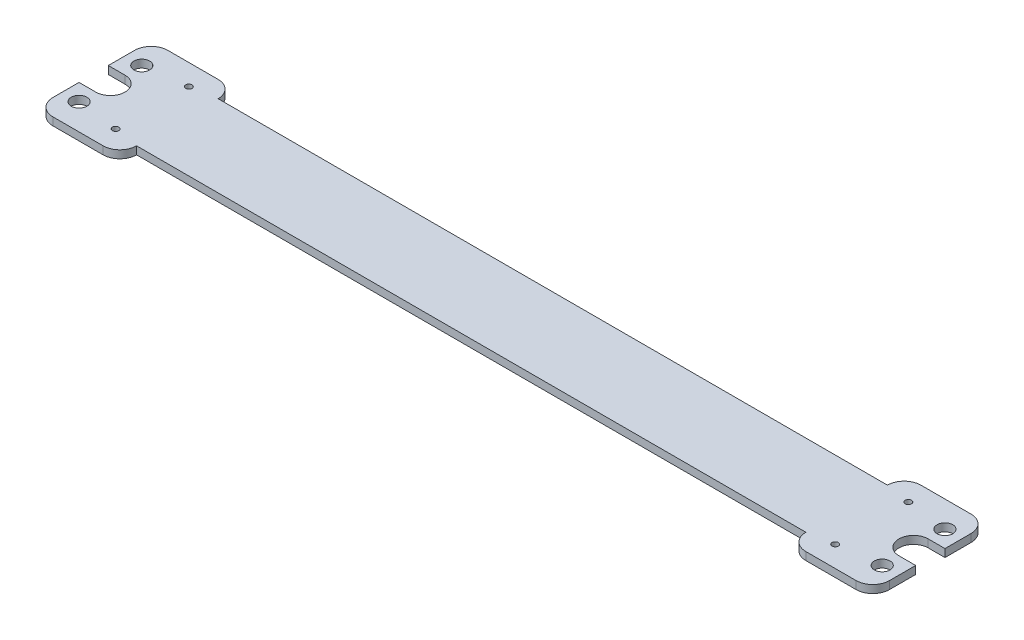
SolidWorks part; units mm, degrees
ref_plane "Front Plane" through (0, 0, 0) normal (0, 0, 1) x (1, 0, 0)
ref_plane "Top Plane" through (0, 0, 0) normal (0, 1, 0) x (1, 0, 0)
ref_plane "Right Plane" through (0, 0, 0) normal (1, 0, 0) x (0, 0, -1)
sketch "Sketch1" plane through (0, 0, 0) normal (0, 1, 0) x (1, 0, 0)
  line L0 (0, -34.925) -> (1.27, -34.925) construction
  line L1 (10.16, 0) -> (40.64, 0)
  line L2 (0, -10.16) -> (0, -26.035)
  line L3 (10.16, -69.85) -> (40.64, -69.85)
  line L5 (10.16, -43.815) -> (0, -43.815)
  line L6 (10.16, -26.035) -> (0, -26.035)
  line L7 (0, -43.815) -> (0, -59.69)
  line L8 (19.05, -34.925) -> (87.4324, -34.925) construction
  line L15 (50.8, -10.16) -> (254, -10.16)
  line L17 (50.8, -59.69) -> (254, -59.69)
  line L18 (254, -10.16) -> (254, -59.69)
  circle A0 centre (10.16, -53.975) radius 4.7625
  circle A1 centre (10.16, -15.875) radius 4.7625
  arc A2 (10.16, -43.815) -> (10.16, -26.035) centre (10.16, -34.925) ccw
  circle A3 centre (10.16, -15.875) radius 6.35 construction
  circle A4 centre (10.16, -53.975) radius 6.35 construction
  arc A5 (0, -59.69) -> (10.16, -69.85) centre (10.16, -59.69) ccw
  arc A6 (10.16, 0) -> (0, -10.16) centre (10.16, -10.16) ccw
  circle A7 centre (35.56, -57.15) radius 1.905
  circle A8 centre (35.56, -12.7) radius 1.905
  arc A9 (40.64, -69.85) -> (50.8, -59.69) centre (40.64, -59.69) ccw
  arc A10 (40.64, 0) -> (50.8, -10.16) centre (40.64, -10.16) cw
  point P22 (0, -69.85)
  point P25 (0, 0)
  point P31 (52.0714, -59.69)
  point P32 (44.6821, 0)
  point P33 (0, 0)
  point P38 (50.8, -69.85)
  dimension "D3" = 9.525
  dimension "D4" = 9.525
  dimension "D5" = 17.78
  dimension "D10" = 34.925
  dimension "D11" = 12.7
  dimension "D12" = 12.7
  dimension "D13" = 10.16
  dimension "D14" = 3.81
  dimension "D15" = 3.81
  dimension "D22" = 10.16
  dimension "D1" = 69.85
  dimension "D2" = 50.8
  dimension "D6" = 19.05
  dimension "D7" = 19.05
  dimension "D8" = 10.16
  dimension "D9" = 10.16
  dimension "D16" = 12.7
  dimension "D17" = 12.7
  dimension "D18" = 203.2
  dimension "D19" = 49.53
  dimension "D20" = 50.8
  dimension "D21" = 24.765
extrude "Boss-Extrude1" add sketch "Sketch1" along normal blind 4.7625
mirror "Mirror1" about plane through (254, 4.7625, 10.16) normal (-1, 0, 0) of "Boss-Extrude1"
